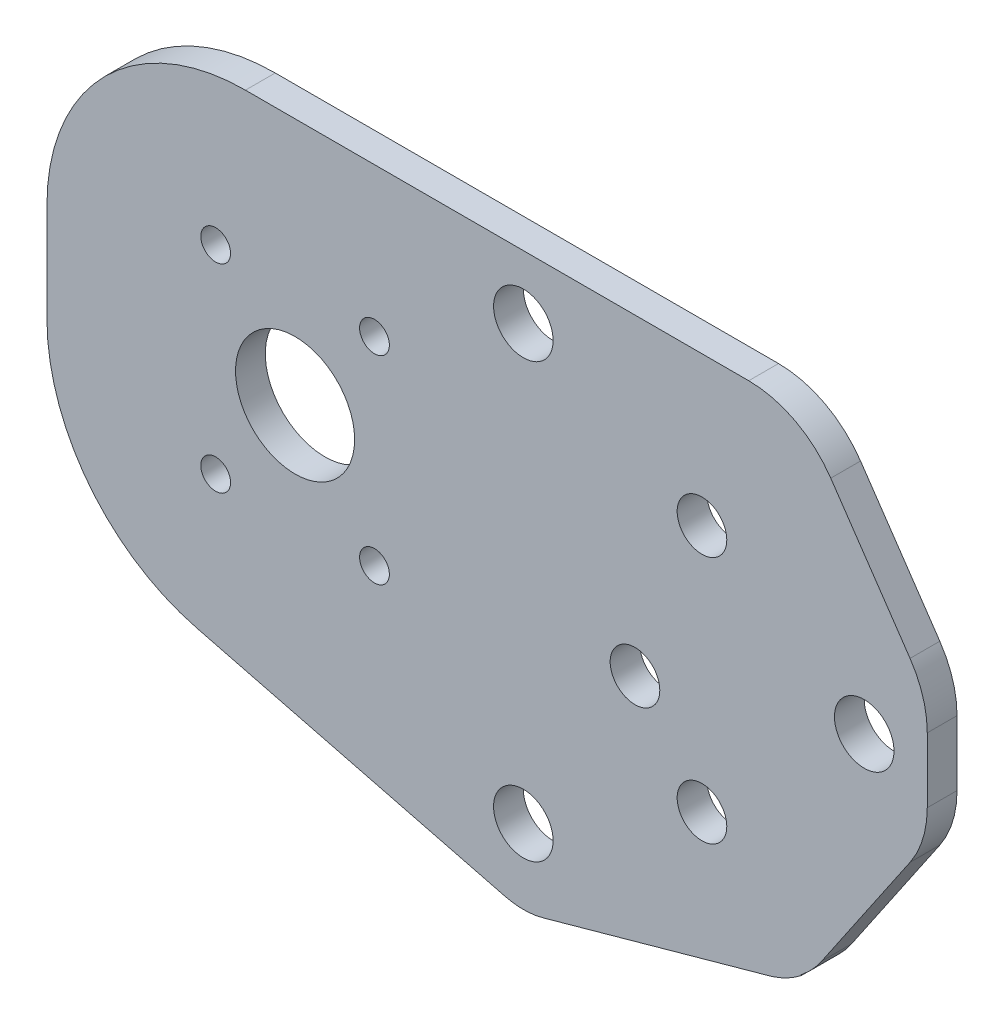
SolidWorks part; units mm, degrees
ref_plane "Plano frontal" through (0, 0, 0) normal (0, 0, 1) x (1, 0, 0)
ref_plane "Plano superior" through (0, 0, 0) normal (0, 1, 0) x (1, 0, 0)
ref_plane "Plano direito" through (0, 0, 0) normal (1, 0, 0) x (0, 0, -1)
sketch "Esboço1" plane through (0, 0, 0) normal (0, 0, 1) x (1, 0, 0)
  line L0 (56, 50) -> (56, 0) construction
  line L1 (0, 0) -> (76, 0)
  line L2 (0, 0) -> (0, 50)
  line L3 (0, 50) -> (76, 50)
  line L4 (76, 0) -> (76, 50)
  line L5 (66, 50) -> (66, 18.5) construction
  line L6 (65.25, 50) -> (65.25, 18.5) construction
  line L7 (59.25, 12.5) -> (25, 12.5) construction
  circle A0 centre (25, 25) radius 16 construction
  circle A1 centre (59.25, 18.5) radius 9.75 construction
  circle A2 centre (59.25, 18.5) radius 6 construction
  circle A3 centre (25, 25) radius 12.5 construction
  circle A4 centre (59.25, 18.5) radius 2.5
  circle A5 centre (25, 25) radius 6
  circle A6 centre (17, 38.8564) radius 1.5 construction
  circle A7 centre (33, 38.8564) radius 1.5 construction
  circle A8 centre (41, 25) radius 1.5 construction
  circle A9 centre (33, 11.1436) radius 1.5 construction
  circle A10 centre (17, 11.1436) radius 1.5 construction
  circle A11 centre (9, 25) radius 1.5 construction
  point P7 (41, 25)
  point P36 (25, 25)
  dimension "D1" = 32
  dimension "D5" = 12
  dimension "D6" = 19.5
  dimension "D9" = 25
  dimension "D10" = 5
  dimension "D13" = 12
  dimension "D14" = 3
  dimension "D2" = 25
  dimension "D3" = 35
  dimension "D4" = 20
  dimension "D7" = 0.75
  dimension "D8" = 10
  dimension "D11" = 25
  dimension "D12" = 50
  dimension "D15" = 6
extrude "Ressalto-extrusão1" add sketch "Esboço1" along normal blind 3
sketch "Esboço2" plane through (0, 0, 3) normal (0, 0, 1) x (1, 0, 0)
  line L0 (66, 50) -> (66, 0) construction
  line L1 (76, 50) -> (0, 50) construction
  line L2 (0, 0) -> (76, 0) construction
  line L3 (76, 0) -> (76, 50) construction
  circle A0 centre (66, 35) radius 2.5
  circle A1 centre (66, 10) radius 2.5
  dimension "D2" = 5
  dimension "D3" = 5
  dimension "D1" = 10
  dimension "D4" = 10
  dimension "D5" = 15
extrude "Corte-extrusão1" cut sketch "Esboço2" against normal blind 3
fillet "Filete1" radius 20 2 edges at (0, 0, 1.5) (0, 50, 1.5)
sketch "Esboço3" plane through (0, 0, 3) normal (0, 0, 1) x (1, 0, 0)
  line L1 (17, 15) -> (33, 15) construction
  line L2 (17, 15) -> (17, 35) construction
  line L3 (17, 35) -> (33, 35) construction
  line L4 (33, 15) -> (33, 35) construction
  line L5 (17, 15) -> (33, 35) construction
  line L6 (17, 35) -> (33, 15) construction
  circle A0 centre (33, 35) radius 1.5
  circle A1 centre (33, 15) radius 1.5
  circle A2 centre (17, 15) radius 1.5
  circle A3 centre (17, 35) radius 1.5
  point P0 (25, 25)
  dimension "D3" = 3
  dimension "D1" = 20
  dimension "D2" = 16
extrude "Corte-extrusão2" cut sketch "Esboço3" against normal through all
sketch "Esboço4" plane through (0, 0, 3) normal (0, 0, 1) x (1, 0, 0)
  line L0 (76, 50) -> (20, 50) construction
  line L1 (55.3323, 43.65) -> (51.6662, 50) construction
  line L2 (51.6662, 50) -> (44.3338, 50) construction
  line L3 (44.3338, 50) -> (40.6677, 43.65) construction
  line L4 (40.6677, 43.65) -> (44.3338, 37.3) construction
  line L5 (44.3338, 37.3) -> (51.6662, 37.3) construction
  line L6 (51.6662, 37.3) -> (55.3323, 43.65) construction
  line L7 (76, 0) -> (76, 50) construction
  line L9 (51.4498, -6.4701) -> (55.3282, -0.2474) construction
  line L10 (55.3282, -0.2474) -> (51.8783, 6.2227) construction
  line L11 (51.8783, 6.2227) -> (44.5502, 6.4701) construction
  line L12 (44.5502, 6.4701) -> (40.6718, 0.2474) construction
  line L13 (40.6718, 0.2474) -> (44.1217, -6.2227) construction
  line L14 (44.1217, -6.2227) -> (51.4498, -6.4701) construction
  line L15 (25, 12.5) -> (61.6574, 12.5) construction
  line L16 (20, 0) -> (76, 0) construction
  line L17 (48, 43.65) -> (48, 0) construction
  circle A0 centre (48, 43.65) radius 3
  circle A1 centre (48, 43.65) radius 6.35 construction
  circle A2 centre (48, 0) radius 3
  circle A3 centre (48, 0) radius 6.35 construction
  arc A4 (17.8926, 14.7172) -> (30.3514, 13.7035) centre (25, 25) ccw construction
  arc A5 (17.8926, 14.7172) -> (30.3514, 13.7035) centre (25, 25) ccw construction
  dimension "D1" = 12.7
  dimension "D3" = 6
  dimension "D2" = 28
extrude "Corte-extrusão3" cut sketch "Esboço4" against normal through all
sketch "Esboço5" plane through (0, 0, 0) normal (0, 0, -1) x (-1, 0, 0)
  line L0 (-76, 0) -> (-50.0089, -7.2259)
  line L1 (-46.1556, -7.2697) -> (-15.0816, 0.6142)
  line L2 (-20, 0) -> (-45, 0) construction
  line L3 (-51, 0) -> (-76, 0) construction
  line L4 (-20, 0) -> (-45, 0)
  line L5 (-51, 0) -> (-76, 0)
  circle A0 centre (-48, 0) radius 3
  arc A1 (-50.0089, -7.2259) -> (-46.1556, -7.2697) centre (-48, 0) ccw
  arc A2 (-20, 0) -> (0, 20) centre (-20, 20) ccw construction
  line M5 (-45, 0) -> (-20, 0)
  arc M6 (-20, 0) -> (0, 20) centre (-20, 20) ccw
  line M11 (-76, 0) -> (-51, 0)
  dimension "D1" = 15
extrude "Ressalto-extrusão2" add sketch "Esboço5" against normal through all contours L0 A1 L1 A0 M6 M5 M11 region at (63.5, -0.6146, 0)
sketch "Esboço6" plane through (0, 0, 0) normal (0, 0, -1) x (-1, 0, 0)
  line L7 (-86.9656, 16.103) -> (-78.0603, 3.0256)
  line L8 (-72.4733, -0.9805) -> (-50.0089, -7.2259)
  line L9 (-46.1556, -7.2697) -> (-15.0816, 0.6142)
  line L10 (0, 20) -> (0, 30)
  line L11 (-20, 50) -> (-70.7112, 50)
  line L12 (-78.9768, 45.6286) -> (-86.9656, 33.897)
  line L13 (-88.7, 28.2685) -> (-88.7, 21.7315)
  line L14 (-86.9656, 16.103) -> (-78.0603, 3.0256)
  line L15 (-72.4733, -0.9805) -> (-50.0089, -7.2259)
  line L16 (-46.1556, -7.2697) -> (-15.0816, 0.6142)
  line L17 (0, 20) -> (0, 30)
  line L18 (-20, 50) -> (-70.7112, 50)
  line L19 (-78.9768, 45.6286) -> (-86.9656, 33.897)
  line L20 (-88.7, 28.2685) -> (-88.7, 21.7315)
  circle A0 centre (-82.35, 25) radius 3 construction
  circle A1 centre (-82.35, 25) radius 3
  arc A7 (-78.0603, 3.0256) -> (-72.4733, -0.9805) centre (-69.7947, 8.6541) ccw
  arc A8 (-50.0089, -7.2259) -> (-46.1556, -7.2697) centre (-48, 0) ccw
  arc A9 (-15.0816, 0.6142) -> (0, 20) centre (-20, 20) ccw
  arc A10 (0, 30) -> (-20, 50) centre (-20, 30) ccw
  arc A11 (-70.7112, 50) -> (-78.9768, 45.6286) centre (-70.7112, 40) ccw
  arc A12 (-86.9656, 33.897) -> (-88.7, 28.2685) centre (-78.7, 28.2685) ccw
  arc A13 (-88.7, 21.7315) -> (-86.9656, 16.103) centre (-78.7, 21.7315) ccw
  arc A15 (-50.0089, -7.2259) -> (-46.1556, -7.2697) centre (-48, 0) ccw
  arc A16 (-15.0816, 0.6142) -> (0, 20) centre (-20, 20) ccw
  arc A17 (0, 30) -> (-20, 50) centre (-20, 30) ccw
  arc A18 (-70.7112, 50) -> (-78.9768, 45.6286) centre (-70.7112, 40) ccw
  arc A19 (-86.9656, 33.897) -> (-88.7, 28.2685) centre (-78.7, 28.2685) ccw
  arc A20 (-88.7, 21.7315) -> (-86.9656, 16.103) centre (-78.7, 21.7315) ccw
  arc A54 (-78.0603, 3.0256) -> (-72.4733, -0.9805) centre (-69.7947, 8.6541) ccw
  line M16 (-76, 50) -> (-76, 0)
  dimension "D1" = 0
extrude "Ressalto-extrusão3" add sketch "Esboço6" against normal through all contours L20 A20 L14 A54 A18 L19 A19 A1 M16 region at (87.7851, 18.9319, 0)
sketch "Esboço7" plane through (0, 0, 0) normal (0, 0, -1) x (-1, 0, 0)
  line L0 (-76, 0) -> (-50.0089, -7.2259) construction
  line L9 (-76, 0.8122) -> (-76, 0)
  line L10 (-76, 0) -> (-50.0089, -7.2259)
  line L11 (-46.1556, -7.2697) -> (-15.0816, 0.6142)
  line L12 (0, 20) -> (0, 30)
  line L13 (-20, 50) -> (-76, 50)
  line L15 (-78.9768, 45.6286) -> (-86.9656, 33.897)
  line L16 (-88.7, 28.2685) -> (-88.7, 21.7315)
  line L17 (-86.9656, 16.103) -> (-78.0603, 3.0256)
  line L18 (-76, 0.8122) -> (-76, 0)
  line L19 (-76, 0) -> (-50.0089, -7.2259)
  line L20 (-46.1556, -7.2697) -> (-15.0816, 0.6142)
  line L21 (0, 20) -> (0, 30)
  line L22 (-20, 50) -> (-76, 50)
  line L24 (-78.9768, 45.6286) -> (-86.9656, 33.897)
  line L25 (-88.7, 28.2685) -> (-88.7, 21.7315)
  line L26 (-86.9656, 16.103) -> (-78.0603, 3.0256)
  line L27 (-76, 50) -> (-76, 48.487)
  line L28 (-76, 50) -> (-76, 48.487)
  arc A0 (-78.9768, 45.6286) -> (-70.7112, 50) centre (-70.7112, 40) cw
  arc A1 (-78.0603, 3.0256) -> (-72.4733, -0.9805) centre (-70.3513, 7.878) ccw
  arc A7 (-50.0089, -7.2259) -> (-46.1556, -7.2697) centre (-48, 0) ccw
  arc A8 (-15.0816, 0.6142) -> (0, 20) centre (-20, 20) ccw
  arc A9 (0, 30) -> (-20, 50) centre (-20, 30) ccw
  arc A10 (-76, 48.487) -> (-78.9768, 45.6286) centre (-70.7112, 40) ccw
  arc A11 (-86.9656, 33.897) -> (-88.7, 28.2685) centre (-78.7, 28.2685) ccw
  arc A12 (-88.7, 21.7315) -> (-86.9656, 16.103) centre (-78.7, 21.7315) ccw
  arc A14 (-50.0089, -7.2259) -> (-46.1556, -7.2697) centre (-48, 0) ccw
  arc A15 (-15.0816, 0.6142) -> (0, 20) centre (-20, 20) ccw
  arc A16 (0, 30) -> (-20, 50) centre (-20, 30) ccw
  arc A17 (-76, 48.487) -> (-78.9768, 45.6286) centre (-70.7112, 40) ccw
  arc A18 (-86.9656, 33.897) -> (-88.7, 28.2685) centre (-78.7, 28.2685) ccw
  arc A19 (-88.7, 21.7315) -> (-86.9656, 16.103) centre (-78.7, 21.7315) ccw
  arc A22 (-78.0603, 3.0256) -> (-76, 0.8122) centre (-69.7947, 8.6541) ccw
  arc A23 (-78.0603, 3.0256) -> (-76, 0.8122) centre (-69.7947, 8.6541) ccw
  line M18 (-76, 0.8122) -> (-76, 0)
  line M19 (-76, 0) -> (-50.0089, -7.2259)
  line M26 (-76, 50) -> (-76, 48.487)
  dimension "D1" = 0
extrude "Corte-extrusão4" cut sketch "Esboço7" against normal through all contours A1 M18 M19 | A0 L22 M26 region at (75.2365, 0.0044, 0) region at (74.6987, 49.5527, 0)
